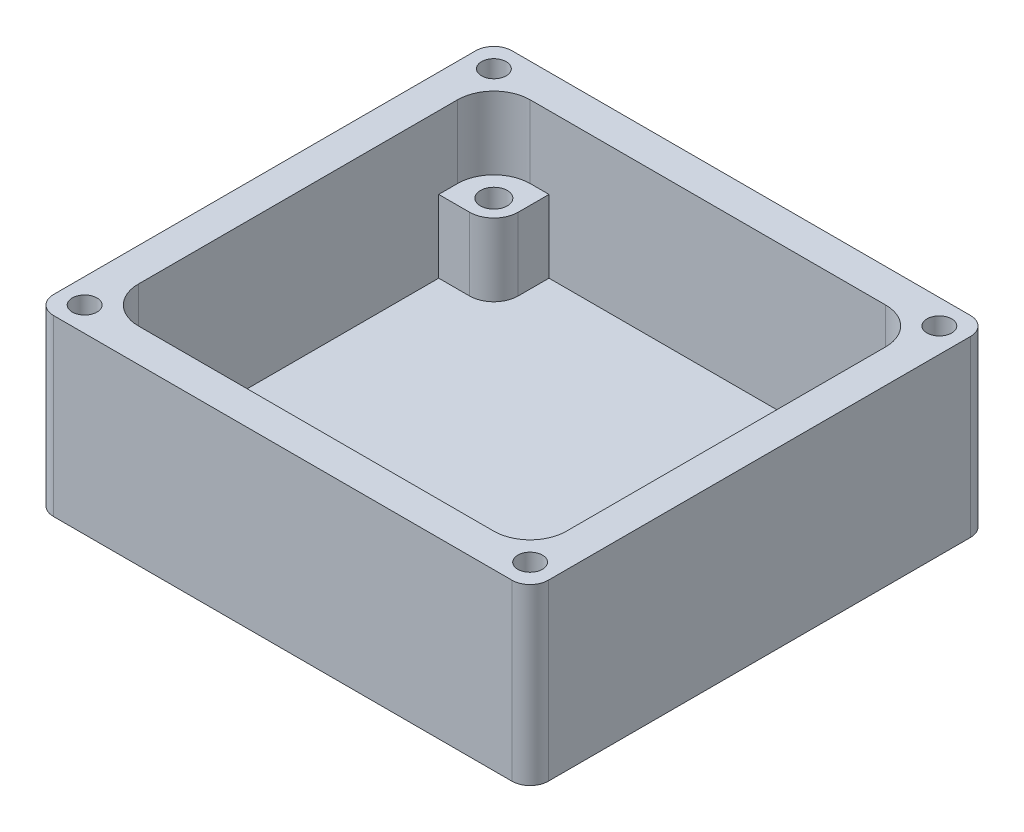
SolidWorks part; units mm, degrees
ref_plane "Front" through (0, 0, 0) normal (0, 0, 1) x (1, 0, 0)
ref_plane "Top" through (0, 0, 0) normal (0, 1, 0) x (1, 0, 0)
ref_plane "Right" through (0, 0, 0) normal (1, 0, 0) x (0, 0, -1)
sketch "ｽｹｯﾁ1" plane through (0, 0, 0) normal (0, 1, 0) x (1, 0, 0)
  line L0 (31.6, 31.6) -> (-31.6, 31.6)
  line L1 (24.5, 27) -> (-24.5, 27)
  line L2 (29.5, 22) -> (29.5, -22)
  line L3 (24.5, -27) -> (-24.5, -27)
  line L4 (-29.5, 22) -> (-29.5, -22)
  line L5 (29.5, 27) -> (-29.5, -27) construction
  line L6 (29.5, -27) -> (-29.5, 27) construction
  line L7 (-34.1, 29.1) -> (-34.1, -29.1)
  line L8 (31.6, -31.6) -> (-31.6, -31.6)
  line L9 (34.1, 29.1) -> (34.1, -29.1)
  line L10 (34.1, 31.6) -> (-34.1, 31.6) construction
  line L11 (34.1, 31.6) -> (34.1, -31.6) construction
  line L12 (34.1, -31.6) -> (-34.1, -31.6) construction
  line L13 (-34.1, 31.6) -> (-34.1, -31.6) construction
  line L14 (29.5, 27) -> (29.5, -27) construction
  line L15 (29.5, -27) -> (-29.5, -27) construction
  line L16 (-29.5, 27) -> (-29.5, -27) construction
  line L17 (29.5, 27) -> (-29.5, 27) construction
  arc A0 (31.6, 31.6) -> (34.1, 29.1) centre (31.6, 29.1) cw
  arc A1 (31.6, -31.6) -> (34.1, -29.1) centre (31.6, -29.1) ccw
  arc A2 (-34.1, -29.1) -> (-31.6, -31.6) centre (-31.6, -29.1) ccw
  arc A3 (-31.6, 31.6) -> (-34.1, 29.1) centre (-31.6, 29.1) ccw
  arc A4 (29.5, -22) -> (24.5, -27) centre (24.5, -22) cw
  arc A5 (-24.5, -27) -> (-29.5, -22) centre (-24.5, -22) cw
  arc A6 (-24.5, 27) -> (-29.5, 22) centre (-24.5, 22) ccw
  arc A7 (24.5, 27) -> (29.5, 22) centre (24.5, 22) cw
  point P0 (0, 0)
  dimension "D4" = 2.5
  dimension "D5" = 5
  dimension "D1" = 59
  dimension "D2" = 54
  dimension "D3" = 4.6
extrude "ﾎﾞｽ - 押し出し2" add sketch "ｽｹｯﾁ1" along normal blind 20
sketch "ｽｹｯﾁ2" plane through (0, 0, 0) normal (0, -1, 0) x (1, 0, 0)
  line L8 (34.1, -29.1) -> (34.1, 29.1)
  line L9 (31.6, 31.6) -> (-31.6, 31.6)
  line L10 (-34.1, 29.1) -> (-34.1, -29.1)
  line L11 (-31.6, -31.6) -> (31.6, -31.6)
  line L12 (34.1, -29.1) -> (34.1, 29.1)
  line L13 (31.6, 31.6) -> (-31.6, 31.6)
  line L14 (-34.1, 29.1) -> (-34.1, -29.1)
  line L15 (-31.6, -31.6) -> (31.6, -31.6)
  arc A8 (31.6, -31.6) -> (34.1, -29.1) centre (31.6, -29.1) ccw
  arc A9 (34.1, 29.1) -> (31.6, 31.6) centre (31.6, 29.1) ccw
  arc A10 (-31.6, 31.6) -> (-34.1, 29.1) centre (-31.6, 29.1) ccw
  arc A11 (-34.1, -29.1) -> (-31.6, -31.6) centre (-31.6, -29.1) ccw
  arc A12 (31.6, -31.6) -> (34.1, -29.1) centre (31.6, -29.1) ccw
  arc A13 (34.1, 29.1) -> (31.6, 31.6) centre (31.6, 29.1) ccw
  arc A14 (-31.6, 31.6) -> (-34.1, 29.1) centre (-31.6, 29.1) ccw
  arc A15 (-34.1, -29.1) -> (-31.6, -31.6) centre (-31.6, -29.1) ccw
  dimension "D1" = 0
extrude "ﾎﾞｽ - 押し出し3" add sketch "ｽｹｯﾁ2" along normal blind 4
sketch "ｽｹｯﾁ3" plane through (0, 0, 0) normal (0, 1, 0) x (1, 0, 0)
  line L0 (-25.25, -22.75) -> (25.25, -22.75)
  line L1 (25.25, -22.75) -> (25.25, 22.75)
  line L2 (25.25, 22.75) -> (-25.25, 22.75)
  line L3 (-25.25, 22.75) -> (-25.25, -22.75)
  line L4 (29.5, 19.4) -> (21.9, 19.4)
  line L5 (29.5, -22) -> (29.5, 22) construction
  line L6 (21.9, 19.4) -> (21.9, 27)
  line L7 (24.5, 27) -> (-24.5, 27) construction
  line L8 (-29.5, 19.4) -> (-21.9, 19.4)
  line L9 (-29.5, 22) -> (-29.5, -22) construction
  line L10 (-21.9, 19.4) -> (-21.9, 27)
  line L11 (29.5, -19.4) -> (21.9, -19.4)
  line L12 (21.9, -19.4) -> (21.9, -27)
  line L13 (-21.9, -27) -> (-21.9, -19.4)
  line L14 (-24.5, -27) -> (24.5, -27) construction
  line L15 (-21.9, -19.4) -> (-29.5, -19.4)
  circle A0 centre (-25.25, 22.75) radius 1.85
  circle A1 centre (25.25, 22.75) radius 1.85
  circle A2 centre (-25.25, -22.75) radius 1.85
  circle A3 centre (25.25, -22.75) radius 1.85
  circle A4 centre (-25.25, 22.75) radius 3.35
  circle A5 centre (-25.25, -22.75) radius 3.35
  circle A6 centre (25.25, -22.75) radius 3.35
  circle A7 centre (25.25, 22.75) radius 3.35
  point P8 (0, -22.75)
  point P9 (-25.25, 0)
  point P39 (-22.0152, -19.4)
  point P40 (21.9, -26.1031)
  line M7 (29.5, -22) -> (29.5, 22)
  line M8 (24.5, 27) -> (-24.5, 27)
  line M9 (-29.5, 22) -> (-29.5, -22)
  line M10 (-24.5, -27) -> (24.5, -27)
  arc M17 (-29.5, -22) -> (-24.5, -27) centre (-24.5, -22) ccw
  arc M18 (24.5, -27) -> (29.5, -22) centre (24.5, -22) ccw
  arc M19 (29.5, 22) -> (24.5, 27) centre (24.5, 22) ccw
  arc M20 (-24.5, 27) -> (-29.5, 22) centre (-24.5, 22) ccw
  dimension "D3" = 3.7
  dimension "D1" = 50.5
  dimension "D2" = 45.5
  dimension "D4" = 1.5
extrude "ﾎﾞｽ - 押し出し4" add sketch "ｽｹｯﾁ3" along normal blind 10 contours L2 A7 L1 A1 | L1 A7 L2 A1 | L2 A4 L3 A0 | L3 A4 L2 A0 | L3 A5 L0 A2 | L0 A5 L3 A2 | L0 A6 L1 A3 | L1 A6 L0 A3 | A6 L12 L11 M10 M18 M7 | A7 L4 L6 M7 M19 M8 | A5 L15 L13 M9 M17 M10 | A4 L10 L8 M8 M20 M9 region at (-23.5489, 0, 21.0489) region at (-22.65, 0, 22.8448) region at (-22.0075, 0, 24.875) region at (23.5489, 0, 21.0489) region at (25.25, 0, 26.2075) region at (22.65, 0, 22.8448) region at (-27.5518, 0, -25.0518) region at (-27.375, 0, -19.5075) region at (-23.5489, 0, -21.0489) region at (23.5489, 0, -21.0489) region at (27.6948, 0, -20.3052) region at (25.3448, 0, -20.15)
sketch "ｽｹｯﾁ4" plane through (0, 20, 0) normal (0, 1, 0) x (1, 0, 0)
  line L0 (28.0355, -25.5355) -> (33.3678, -30.8678)
  line L1 (33.3678, 30.8678) -> (28.0355, 25.5355)
  line L2 (-28.0355, 25.5355) -> (-33.3678, 30.8678)
  line L3 (-33.3678, -30.8678) -> (-28.0355, -25.5355)
  circle A0 centre (30.7017, 28.2017) radius 1.7
  circle A1 centre (-30.7017, 28.2017) radius 1.7
  circle A2 centre (-30.7017, -28.2017) radius 1.7
  circle A3 centre (30.7017, -28.2017) radius 1.7
  arc A6 (31.6, -31.6) -> (34.1, -29.1) centre (31.6, -29.1) ccw construction
  arc A7 (24.5, -27) -> (29.5, -22) centre (24.5, -22) ccw construction
  arc A8 (34.1, 29.1) -> (31.6, 31.6) centre (31.6, 29.1) ccw construction
  arc A9 (29.5, 22) -> (24.5, 27) centre (24.5, 22) ccw construction
  arc A10 (-24.5, 27) -> (-29.5, 22) centre (-24.5, 22) ccw construction
  arc A11 (-31.6, 31.6) -> (-34.1, 29.1) centre (-31.6, 29.1) ccw construction
  arc A12 (-34.1, -29.1) -> (-31.6, -31.6) centre (-31.6, -29.1) ccw construction
  arc A13 (-29.5, -22) -> (-24.5, -27) centre (-24.5, -22) ccw construction
  point P16 (30.7017, -28.2017)
  point P41 (-30.7017, -28.2017)
  point P42 (-30.7017, 28.2017)
  point P43 (30.7017, 28.2017)
  dimension "D1" = 3.4
extrude "ｶｯﾄ - 押し出し1" cut sketch "ｽｹｯﾁ4" against normal through all contours L3 A2 | L3 A2 | L2 A1 | L2 A1 | L1 A0 | L1 A0 | L0 A3 | L0 A3 region at (31.2118, 20, 27.6915) region at (30.1915, 20, 28.7118) region at (31.2118, 20, -27.6915) region at (30.1915, 20, -28.7118) region at (-31.2118, 20, -27.6915) region at (-30.1915, 20, -28.7118) region at (-31.2118, 20, 27.6915) region at (-30.1915, 20, 28.7118)
